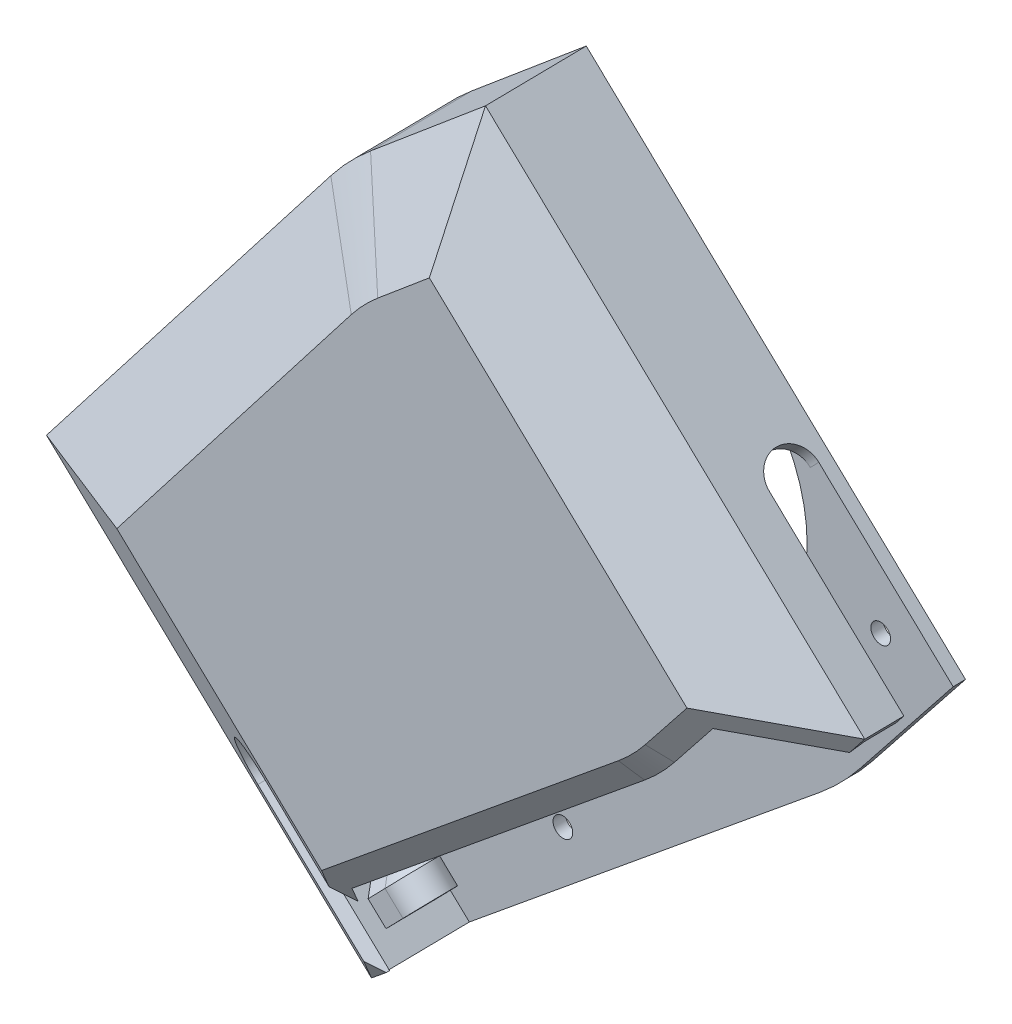
SolidWorks part; units mm, degrees
material "ABS"
ref_plane "Front Plane" through (0, 0, 0) normal (0, 0, 1) x (1, 0, 0)
ref_plane "Top Plane" through (0, 0, 0) normal (0, 1, 0) x (1, 0, 0)
ref_plane "Right Plane" through (0, 0, 0) normal (1, 0, 0) x (0, 0, -1)
sketch "Sketch1" plane through (0, 1.5399, -108.8354) normal (0, -0.0141, 0.9999) x (1, 0, 0)
  line L0 (-63.9977, 99.1574) -> (-31.4443, 126.5628) construction
  line L1 (-138.5132, 4.9856) -> (-70.5336, 92.3642) construction
  line L2 (-6.4305, 29.9782) -> (-91.9316, -40.3482) construction
  line L3 (77.4087, 133.6531) -> (0.1827, 36.6962) construction
  line L4 (-63.9977, 99.1574) -> (-45.1299, 115.0415)
  line L5 (-117.5072, 31.9859) -> (-70.5336, 92.3642)
  line L6 (-6.4305, 29.9782) -> (-65.5114, -18.6171)
  line L7 (15.5488, 55.9882) -> (0.1827, 36.6962)
  line L8 (15.5488, 55.9882) -> (-45.1299, 115.0415)
  line L9 (-65.5114, -18.6171) -> (-117.5072, 31.9859)
  line L10 (-91.9316, -40.3482) -> (-138.5132, 4.9856) construction
  line L12 (12.3039, 59.1462) -> (4.8233, 66.4264) construction
  arc A0 (-63.9977, 99.1574) -> (-70.5336, 92.3642) centre (-35.0164, 64.7323) ccw construction
  arc A1 (-6.4305, 29.9782) -> (0.1827, 36.6962) centre (-35.0164, 64.7323) ccw construction
  arc A2 (-63.9977, 99.1574) -> (-70.5336, 92.3642) centre (-35.0164, 64.7323) ccw
  arc A3 (-6.4305, 29.9782) -> (0.1827, 36.6962) centre (-35.0164, 64.7323) ccw
  dimension "D1" = 110
extrude "Extrude1" add sketch "Sketch1" along normal blind 25 contours L4 L8 L7 A3 L6 L9 L5 A2
chamfer "Chamfer1" distance 15 angle 30 8 edges at (-14.7906, 86.6925, -82.628) (7.8658, 47.5238, -83.1822) (-54.5638, 108.2749, -82.3227) (-2.9475, 34.3465, -83.3687) (-67.444, 97.109, -82.4807) (-35.9709, 6.8662, -83.7575) (-91.5093, 7.87, -83.7433) (-94.0204, 63.3551, -82.9582) first distance on face at (-44.1726, 56.5047, -83.0552)
ref_plane "Plane1" through (-24.3398, 23.6854, 0.3351) normal (-0.7166, 0.6974, 0.0099) x (0, 0.0141, -0.9999)
sketch "Sketch3" plane through (-26.3027, 21.6687, 0.3066) normal (0.7166, -0.6974, -0.0099) x (-0.0077, 0.0062, -1)
  line L0 (106.2666, 52.9614) -> (107.4397, -53.0321)
  line L1 (107.4397, -53.0321) -> (94.2555, -53.178)
  line L2 (94.2555, -53.178) -> (86.2912, -39.7294)
  line L3 (86.2912, -39.7294) -> (85.4177, 39.194)
  line L4 (85.4177, 39.194) -> (93.0824, 52.8155)
  line L5 (93.0824, 52.8155) -> (106.2666, 52.9614)
  line L6 (91.9056, 54.8026) -> (108.2444, 54.9835) construction
  line L7 (107.151, 153.779) -> (108.516, 30.4426) construction
  line L10 (84.2973, -40.2874) -> (93.123, -55.1906) construction
  line L11 (84.2973, -40.2874) -> (83.6035, 22.3961) construction
  line L12 (91.9056, 54.8026) -> (83.4119, 39.7077) construction
  line L13 (83.534, 28.6801) -> (83.4119, 39.7077) construction
  line L15 (93.123, -55.1906) -> (109.4617, -55.0098) construction
  line L16 (108.6203, 21.0165) -> (109.4617, -55.0098) construction
  dimension "D1" = 2
  dimension "D2" = 2
  dimension "D3" = 2
  dimension "D4" = 2
  dimension "D5" = 2
  dimension "D6" = 2
extrude "Cut-Extrude2" cut sketch "Sketch3" against normal blind 15 and the other way blind 15
shell "Shell1" thickness 2 removed face at (-37.9016, 32.607, -94.9994)
sketch "Sketch5" plane through (0, 1.5116, -106.8356) normal (0, -0.0141, 0.9999) x (1, 0, 0)
  circle A0 centre (-35.0164, 64.7323) radius 27
  dimension "D1" = 54
extrude "Cut-Extrude3" cut sketch "Sketch5" against normal blind 15
sketch "Sketch6" plane through (17.6442, 18.748, -43.5573) normal (-0.3487, -0.3705, 0.8609) x (0.9372, -0.1379, 0.3203)
  line L0 (-102.7872, -29.3525) -> (-81.1427, -47.5951) construction
  line L1 (-98.9204, -24.7647) -> (-77.276, -43.0072)
  line L2 (-106.654, -33.9403) -> (-85.0095, -52.1829)
  line L3 (-88.7252, -52.5698) -> (-144.2036, -5.8111) construction
  line L4 (-87.8287, -30.6735) -> (-88.7252, -52.5698) construction
  arc A0 (-98.9204, -24.7647) -> (-106.654, -33.9403) centre (-102.7872, -29.3525) ccw
  arc A1 (-85.0095, -52.1829) -> (-77.276, -43.0072) centre (-81.1427, -47.5951) ccw
  point P2 (-91.965, -38.4738)
  dimension "D1" = 6
  dimension "D2" = 15
extrude "Cut-Extrude4" cut sketch "Sketch6" against normal blind 5
sketch "Sketch7" plane through (35.5471, 36.5219, 0.5167) normal (0.6974, 0.7166, 0.0101) x (0.7166, -0.6974, -0.0099)
  line L0 (-20.9692, 102.8462) -> (-57.9057, 102.8462) construction
  line L1 (-20.9692, 98.8462) -> (-57.9057, 98.8462)
  line L2 (-20.9692, 106.8462) -> (-57.9057, 106.8462)
  line L3 (-27.7066, 106.8462) -> (-70.2412, 106.8462) construction
  line L4 (-27.9057, 92.5065) -> (-27.9057, 108.8462) construction
  arc A0 (-20.9692, 98.8462) -> (-20.9692, 106.8462) centre (-20.9692, 102.8462) ccw
  arc A1 (-57.9057, 106.8462) -> (-57.9057, 98.8462) centre (-57.9057, 102.8462) ccw
  point P2 (-39.4375, 102.8462)
  dimension "D1" = 4
  dimension "D2" = 30
extrude "Cut-Extrude5" cut sketch "Sketch7" against normal blind 5
sketch "Sketch8" plane through (0, 1.5116, -106.8356) normal (0, -0.0141, 0.9999) x (1, 0, 0)
  line L0 (-95.4785, 49.6185) -> (-48.4904, 3.8891) construction
  line L1 (-95.4785, 49.6185) -> (-43.1702, 103.3665) construction
  line L2 (-48.4904, 3.8891) -> (3.8178, 57.6371) construction
  line L3 (-43.1702, 103.3665) -> (3.8178, 57.6371) construction
  line L4 (-63.9573, -17.3388) -> (-114.8295, 32.1707) construction
  line L5 (-16.1854, 84.0816) -> (-45.2271, 112.3453) construction
  circle A0 centre (-95.4785, 49.6185) radius 1.6
  circle A1 centre (-48.4904, 3.8891) radius 1.6
  circle A2 centre (-43.1702, 103.3665) radius 1.6
  circle A3 centre (3.8178, 57.6371) radius 1.6
  dimension "D5" = 3.2
  dimension "D1" = 5
  dimension "D2" = 75
  dimension "D3" = 12
  dimension "D4" = 10
extrude "Cut-Extrude6" cut sketch "Sketch8" against normal blind 5
ref_plane "Plane2" through (-24.3398, 23.6854, 0.3351) normal (-0.7166, 0.6974, 0.0099) x (0, 0.0141, -0.9999)
ref_plane "Plane3" through (-27.2063, 26.4749, 0.3746) normal (-0.7166, 0.6974, 0.0099) x (0, 0.0141, -0.9999)
sketch "Sketch9" plane through (-27.2063, 26.4749, 0.3746) normal (-0.7166, 0.6974, 0.0099) x (0, 0.0141, -0.9999)
  line L0 (104.3937, 57.0322) -> (96.3937, 57.0322)
  line L1 (104.3937, 57.0322) -> (104.3937, 53.0322)
  line L2 (96.3937, 57.0322) -> (96.3937, 53.0322)
  line L4 (106.8462, 57.0322) -> (93.6612, 57.0322) construction
  line L6 (96.813, -49.9209) -> (99.048, -46.9707)
  line L7 (90.5858, -44.8927) -> (92.6713, -42.1399)
  line L9 (96.813, -49.9209) -> (93.2029, -49.9209)
  line L10 (93.2029, -49.9209) -> (90.5858, -44.8927)
  arc A0 (104.3937, 53.0322) -> (96.3937, 53.0322) centre (100.3937, 53.0322) cw
  arc A1 (99.048, -46.9707) -> (92.6713, -42.1399) centre (95.8596, -44.5553) ccw
  circle A2 centre (100.3937, 53.0322) radius 1.3
  circle A3 centre (95.8596, -44.5553) radius 1.3
  circle A4 centre (95.8596, -44.5553) radius 3 construction
  dimension "D1" = 2.6
  dimension "D2" = 4
  dimension "D4" = 6
  dimension "D3" = 4
extrude "Extrude2" add sketch "Sketch9" along normal blind 8
chamfer "Chamfer2" distance 4 angle 45 6 edges at (-71.3213, -5.9036, -104.4877) (-67.1366, -1.6607, -100.4273) (-71.3213, -6.0167, -96.4885) (0.5164, 67.8177, -97.3418) (-4.0884, 63.0865, -97.3923) (-2.7781, 64.3415, -90.9324)
